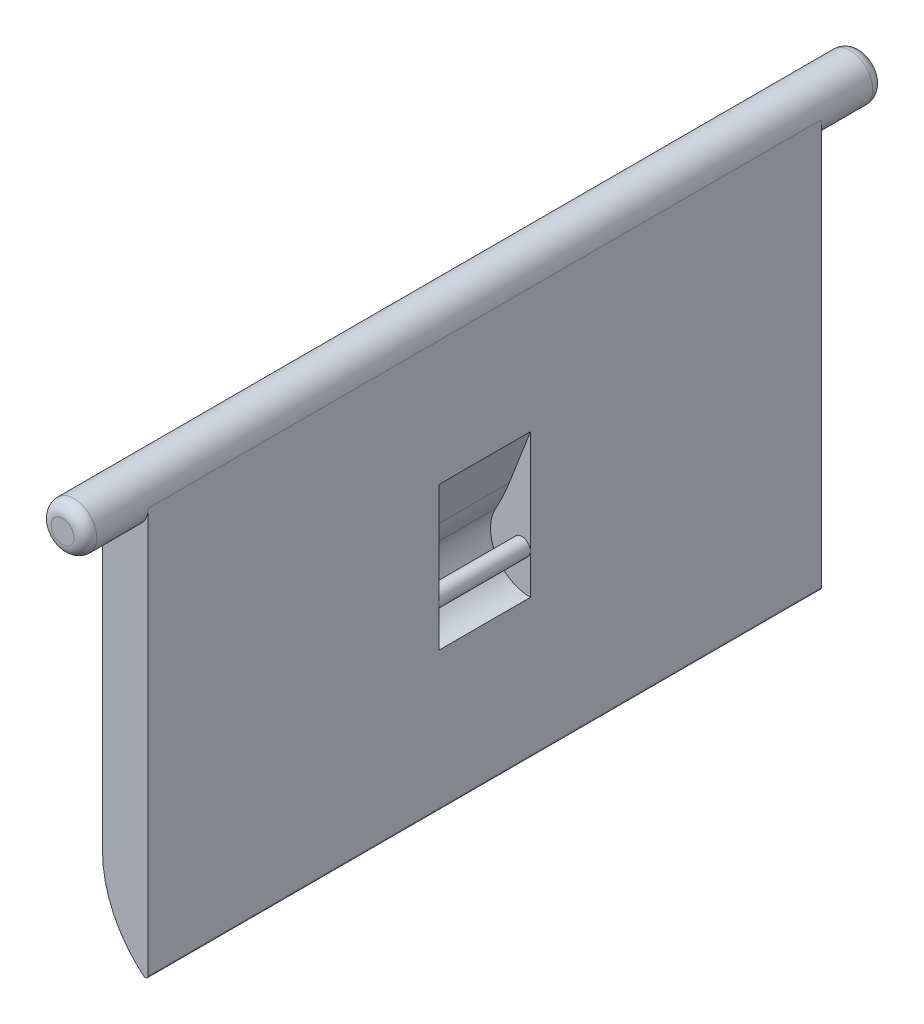
SolidWorks part; units mm, degrees
note: The reader was unsure of these and kept them because the rebuilt part matched: shared geometry of "Sketch3<4>".
material "ABS"
ref_plane "Front" through (0, 0, 0) normal (0, 0, 1) x (1, 0, 0)
ref_plane "Top" through (0, 0, 0) normal (0, 1, 0) x (1, 0, 0)
ref_plane "Right" through (0, 0, 0) normal (1, 0, 0) x (0, 0, -1)
sketch "Sketch3" plane through (0, 0, 0) normal (0, 0, 1) x (1, 0, 0)
  line L0 (2, 0) -> (2, -36)
  line L1 (-2, 0) -> (-2, -28)
  arc A0 (2, 0) -> (-2, 0) centre (0, 0) ccw
  arc A1 (-2, -28) -> (2, -36) centre (8, -28) ccw
  circle A2 centre (0, 0) radius 2
  dimension "D1" = 4
  dimension "D2" = 10
  dimension "D3" = 38
extrude "Boss-Extrude1" add sketch "Sketch3" along normal mid plane 59 contours A2 L1 A1 L0
extrude "Boss-Extrude2" add sketch "Sketch3<4>" along normal mid plane 70 contours A0 A2
sketch "Sketch3<4>" plane through (0, 0, 0) normal (0, 0, 1) x (1, 0, 0) same geometry as "Sketch3"
fillet "Fillet1" radius 1 2 edges at (2, 0, -35) (2, 0, 35)
fillet "Fillet2" radius 0.25 1 edges at (2, -36, 0)
sketch "Sketch4" plane through (0, 0, 0) normal (0, 0, 1) x (1, 0, 0)
  line L0 (2, 0) -> (2, -35.4833) construction
  circle A0 centre (2, -20) radius 3.5
  dimension "D1" = 7
  dimension "D2" = 20
extrude "Cut-Extrude1" cut sketch "Sketch4" against normal mid plane 8
sketch "Sketch5" plane through (0, 0, 0) normal (0, 0, 1) x (1, 0, 0)
  line L0 (2, -16.5) -> (2, -23.5) construction
  line L2 (2, -23.5) -> (2, -16.5)
  line L3 (2, -23.5) -> (2, -16.5) construction
  circle A0 centre (1.25, -20) radius 0.75
  arc A2 (2, -16.5) -> (2, -23.5) centre (2, -20) ccw
  arc A3 (2, -16.5) -> (2, -23.5) centre (2, -20) ccw construction
  point P6 (-1.5, -20)
  dimension "D2" = 1.5
  dimension "D1" = 0
extrude "Boss-Extrude3" add sketch "Sketch5" along normal mid plane 10
chamfer "Chamfer1" distance 10 angle 45 1 edges at (2, -16.5, 0)
fillet "Fillet3" radius 20 1 edges at (-0.5926, -17.6487, 0)
